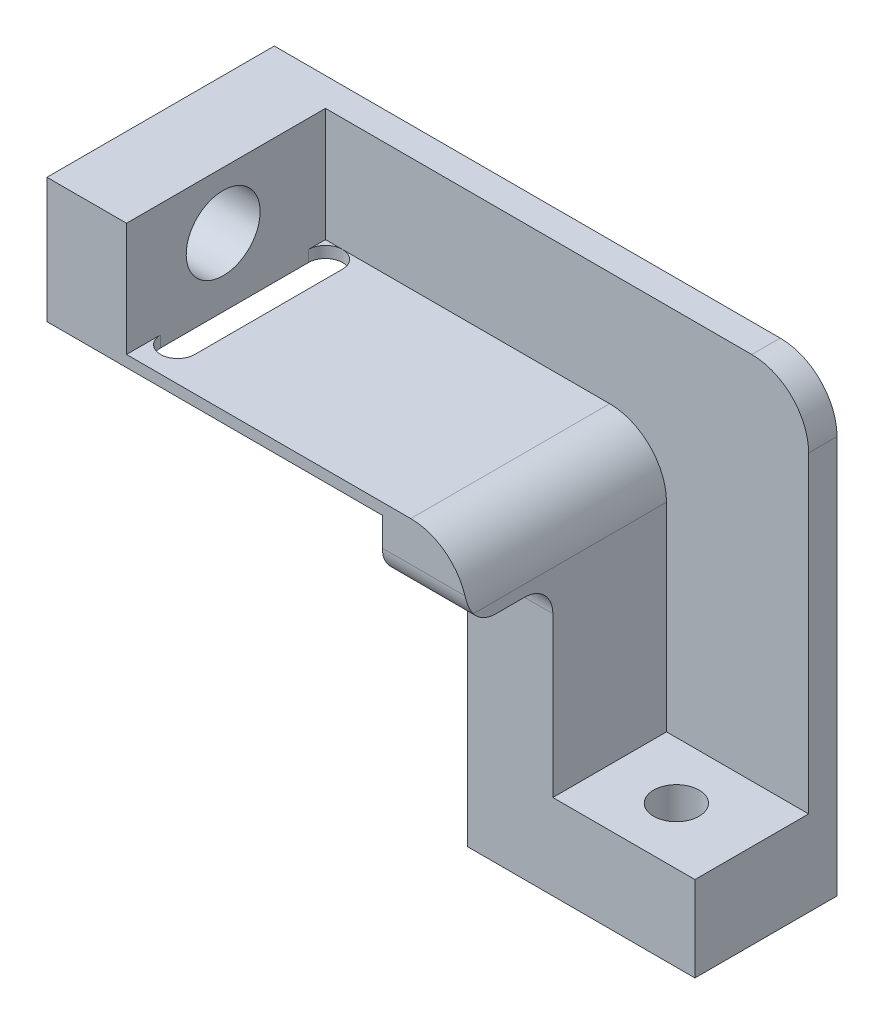
SolidWorks part; units mm, degrees
material "ABS"
ref_plane "Front Plane" through (0, 0, 0) normal (0, 0, 1) x (1, 0, 0)
ref_plane "Top Plane" through (0, 0, 0) normal (0, 1, 0) x (1, 0, 0)
ref_plane "Right Plane" through (0, 0, 0) normal (1, 0, 0) x (0, 0, -1)
sketch "Sketch1" plane through (0, 0, 0) normal (0, 0, 1) x (1, 0, 0)
  line L0 (40, -23.3254) -> (0, -23.3254)
  line L1 (0, -23.3254) -> (0, 34.6746)
  line L7 (15, 56.6746) -> (15, -8.3254)
  line L8 (15, -8.3254) -> (40, -8.3254)
  line L9 (40, -8.3254) -> (40, -23.3254)
  line L10 (15, 56.6746) -> (-59, 56.6746)
  line L11 (-59, 56.6746) -> (-59, 34.6746)
  line L12 (-59, 34.6746) -> (0, 34.6746)
  dimension "D1" = 40
  dimension "D2" = 80
  dimension "D3" = 22
  dimension "D4" = 15
  dimension "D5" = 15
  dimension "D6" = 74
extrude "Boss-Extrude1" add sketch "Sketch1" along normal blind 40
sketch "Sketch2" plane through (0, -8.3254, 0) normal (0, 1, 0) x (1, 0, 0)
  line L0 (40, 0) -> (15, 0) construction
  circle A0 centre (26.7302, -15) radius 4
  dimension "D1" = 8
  dimension "D2" = 15
extrude "Cut-Extrude1" cut sketch "Sketch2" against normal blind 30
sketch "Sketch3" plane through (-59, 0, 0) normal (1, 0, 0) x (0, 0, -1)
  line L2 (-40, -8.3254) -> (-40, 56.6746) construction
  line L3 (-40, 56.6746) -> (0, 56.6746) construction
  circle A0 centre (-23, 46.6746) radius 6.5
  dimension "D1" = 17
  dimension "D2" = 13
  dimension "D3" = 10
extrude "Cut-Extrude2" cut sketch "Sketch3" along normal blind 100 and the other way blind 100
sketch "Sketch5" plane through (15, 0, 0) normal (1, 0, 0) x (0, 0, -1)
  line L0 (-40, 56.6746) -> (0, 56.6746) construction
  line L1 (-40, 56.6746) -> (-5, 56.6746)
  line L2 (-40, 56.6746) -> (-40, 36.6746)
  line L3 (-40, 36.6746) -> (-5, 36.6746)
  line L4 (-5, 56.6746) -> (-5, 36.6746)
  line L5 (-40, -8.3254) -> (-40, 56.6746) construction
  line L6 (0, -8.3254) -> (0, 56.6746) construction
  dimension "D1" = 20
  dimension "D2" = 5
extrude "Cut-Extrude3" cut sketch "Sketch5" against normal blind 60
sketch "Sketch6" plane through (15, 0, 0) normal (1, 0, 0) x (0, 0, -1)
  line L0 (0, -8.3254) -> (0, 56.6746) construction
  line L1 (-5, 56.6746) -> (0, 56.6746)
  line L2 (-5, 56.6746) -> (-5, -8.3254)
  line L3 (-5, -8.3254) -> (0, -8.3254)
  line L4 (0, 56.6746) -> (0, -8.3254)
  line L5 (-40, -8.3254) -> (0, -8.3254) construction
extrude "Boss-Extrude2" add sketch "Sketch6" along normal blind 25
sketch "Sketch7" plane through (0, 36.6746, 0) normal (0, 1, 0) x (1, 0, 0)
  line L0 (-42, -8) -> (-42, -34) construction
  line L1 (-39, -8) -> (-39, -34)
  line L2 (-45, -8) -> (-45, -34)
  line L3 (-45, -40) -> (-45, -5) construction
  line L4 (-45, -5) -> (15, -5) construction
  line L5 (15, -40) -> (-45, -40) construction
  arc A0 (-39, -8) -> (-45, -8) centre (-42, -8) ccw
  arc A1 (-45, -34) -> (-39, -34) centre (-42, -34) ccw
  point P2 (-42, -21)
  dimension "D2" = 3
  dimension "D1" = 3
  dimension "D3" = 3
  dimension "D4" = 6
extrude "Cut-Extrude4" cut sketch "Sketch7" against normal blind 10
fillet "Fillet1" radius 10 2 edges at (15, 36.6746, 22.5) (40, 56.6746, 2.5)
sketch "Sketch8" plane through (0, 0, 40) normal (0, 0, 1) x (1, 0, 0)
  line L0 (0, 34.6746) -> (0, -23.3254) construction
  line L1 (40, -23.3254) -> (0, -23.3254)
  line L2 (40, -23.3254) -> (40, 24.6746)
  line L3 (40, 24.6746) -> (0, 24.6746)
  line L4 (0, -23.3254) -> (0, 24.6746)
  line L5 (-59, 34.6746) -> (0, 34.6746) construction
  dimension "D1" = 10
extrude "Cut-Extrude5" cut sketch "Sketch8" against normal blind 15
fillet "Fillet2" radius 5 2 edges at (7.5, 24.6746, 40) (7.5, 24.6746, 25)
